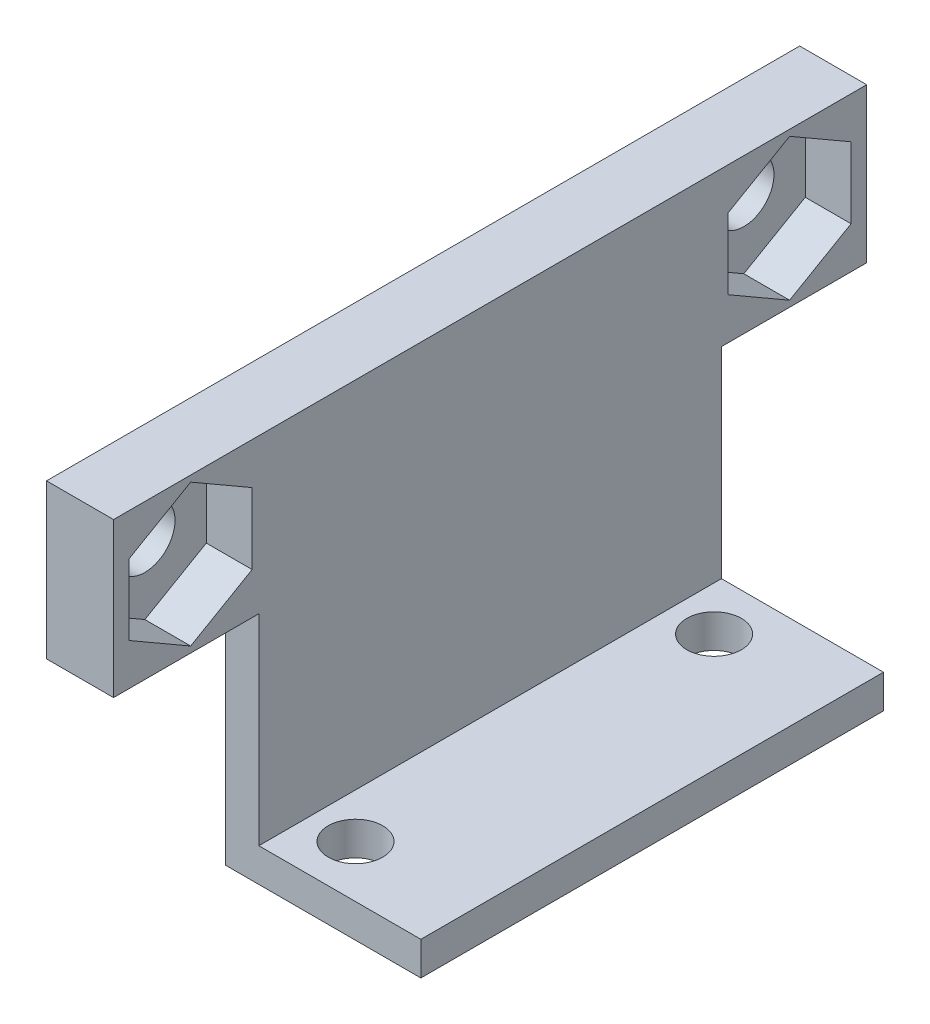
SolidWorks part; units mm, degrees
ref_plane "Front Plane" through (0, 0, 0) normal (0, 0, 1) x (1, 0, 0)
ref_plane "Top Plane" through (0, 0, 0) normal (0, 1, 0) x (1, 0, 0)
ref_plane "Right Plane" through (0, 0, 0) normal (1, 0, 0) x (0, 0, -1)
sketch "Sketch2" plane through (0, 0, 0) normal (0, 1, 0) x (1, 0, 0)
  line L1 (0, 0) -> (17.75, 0)
  line L2 (0, 0) -> (0, 20.7)
  line L3 (0, 20.7) -> (17.75, 20.7)
  line L4 (17.75, 0) -> (17.75, 20.7)
  line L5 (0, 0) -> (17.75, 20.7) construction
  line L6 (0, 20.7) -> (17.75, 0) construction
  circle A1 centre (1.9965, 2.3283) radius 1.22
  circle A2 centre (1.9821, 18.3885) radius 1.22
  point P2 (0, 0)
  point P5 (8.875, 10.35)
  point P9 (1.34, 1.3)
  point P11 (1.3, 19.4)
  point P13 (2.829, 17.4009)
  point P14 (0, 0)
  point P15 (0, 0)
  point P16 (0, 0)
  point P17 (0, 0)
  dimension "D3" = 1.3
  dimension "D5" = 2.44
  dimension "D8" = 2.44
  dimension "D1" = 20.7
  dimension "D2" = 17.75
  dimension "D4" = 1.34
  dimension "D6" = 1.3
  dimension "D7" = 1.3
extrude "Boss-Extrude1" add sketch "Sketch2" along normal blind 1.5
sketch "Sketch5" plane through (0, 0, 0) normal (-1, 0, 0) x (0, 0, 1)
  line L1 (-20.7, 0) -> (0, 0)
  line L2 (-20.7, 0) -> (-20.7, 8.9402)
  line L3 (-20.7, 8.9402) -> (0, 8.9402)
  line L4 (0, 0) -> (0, 8.9402)
  line L5 (-20.7, 0) -> (0, 8.9402) construction
  line L6 (-20.7, 8.9402) -> (0, 0) construction
  point P4 (-10.35, 4.4701)
  dimension "D1" = 8.9402
  dimension "D2" = 20.7
sketch "Sketch12" plane through (17.75, 0, 0) normal (1, 0, 0) x (0, 0, -1)
  point P0 (0, 0)
  point P2 (1.0818, 0.796)
  line M1 (0, 0) -> (20.7, 0)
  line M2 (20.7, 0) -> (20.7, 1.5)
  line M3 (20.7, 1.5) -> (0, 1.5)
  line M4 (0, 1.5) -> (0, 0)
extrude "Cut-Extrude2" cut sketch "Sketch12" against normal blind 10.5 contours M4 M1 M2 M3 region at (17.75, 0.75, -10.35)
extrude "Boss-Extrude3" add sketch "Sketch5" along normal blind 1.5
sketch "Sketch25" plane through (0, 8.9402, 0) normal (0, 1, 0) x (1, 0, 0)
  point P0 (-0.359, 5.5204)
  line M1 (0, 0) -> (0, 20.7)
  line M2 (0, 20.7) -> (-1.5, 20.7)
  line M3 (-1.5, 20.7) -> (-1.5, 0)
  line M4 (-1.5, 0) -> (0, 0)
extrude "Boss-Extrude5" add sketch "Sketch25" along normal blind 4.5 contours M4 M1 M2 M3 region at (-0.75, 8.9402, -10.35)
sketch "Sketch26" plane through (0, 0, 0) normal (1, 0, 0) x (0, 0, -1)
  line L1 (-6.5, 17.3902) -> (27.2, 17.3902)
  line L2 (-6.5, 17.3902) -> (-6.5, 10.4902)
  line L3 (-6.5, 10.4902) -> (27.2, 10.4902)
  line L4 (27.2, 17.3902) -> (27.2, 10.4902)
  line L5 (-6.5, 17.3902) -> (27.2, 10.4902) construction
  line L6 (-6.5, 10.4902) -> (27.2, 17.3902) construction
  line L7 (0, 1.5) -> (0, 13.4402) construction
  line L10 (0, 13.4402) -> (20.7, 13.4402) construction
  circle A1 centre (23.75, 13.9402) radius 1.35
  circle A2 centre (-3.05, 13.9402) radius 1.35
  point P4 (10.35, 13.9402)
  point P5 (24.8487, 10.5286)
  point P6 (-4.1974, 11.8021)
  point P7 (0, 0)
  point P8 (24.8487, 10.5286)
  point P9 (24.8487, 10.5286)
  point P12 (24.4178, 11.8021)
  point P13 (0, 0)
  point P14 (24.0332, 11.8021)
  point P17 (10.35, 11.7955)
  point P19 (-2.9572, 6.6602)
  point P20 (20.7336, 12.0741)
  point P22 (27, 12.6267)
  point P24 (-1.1899, 12.0181)
  point P25 (27.2, 17.3106)
  dimension "D3" = 6.5
  dimension "D1" = 3.45
  dimension "D6" = 2.7
  dimension "D9" = 2.7
  dimension "D2" = 6.9
  dimension "D4" = 6.5
  dimension "D5" = 3.45
  dimension "D7" = 3.45
  dimension "D8" = 3.45
  dimension "D10" = 0.5
extrude "Boss-Extrude9" add sketch "Sketch26" against normal blind 3
sketch "Sketch29" plane through (-1.5, 0, 0) normal (-1, 0, 0) x (0, 0, 1)
  line L0 (6.5, 17.3902) -> (6.5, 10.4902) construction
  line L1 (-26.5, 12.3525) -> (-23.75, 10.7648)
  line L2 (-23.75, 10.7648) -> (-21, 12.3525)
  line L3 (-21, 12.3525) -> (-21, 15.5279)
  line L4 (-21, 15.5279) -> (-23.75, 17.1156)
  line L5 (-23.75, 17.1156) -> (-26.5, 15.5279)
  line L6 (-26.5, 15.5279) -> (-26.5, 12.3525)
  line L7 (0.3, 12.3525) -> (3.05, 10.7648)
  line L8 (-27.2, 10.4902) -> (-27.2, 17.3902) construction
  line L9 (3.05, 10.7648) -> (5.8, 12.3525)
  line L10 (5.8, 12.3525) -> (5.8, 15.5279)
  line L11 (5.8, 15.5279) -> (3.05, 17.1156)
  line L12 (3.05, 17.1156) -> (0.3, 15.5279)
  line L13 (0.3, 15.5279) -> (0.3, 12.3525)
  circle A0 centre (-23.75, 13.9402) radius 2.75 construction
  circle A1 centre (3.05, 13.9402) radius 2.75 construction
  dimension "D1" = 5.5
  dimension "D2" = 5.5
extrude "Cut-Extrude3" cut sketch "Sketch29" against normal blind 1.5 and the other way blind 0.55
